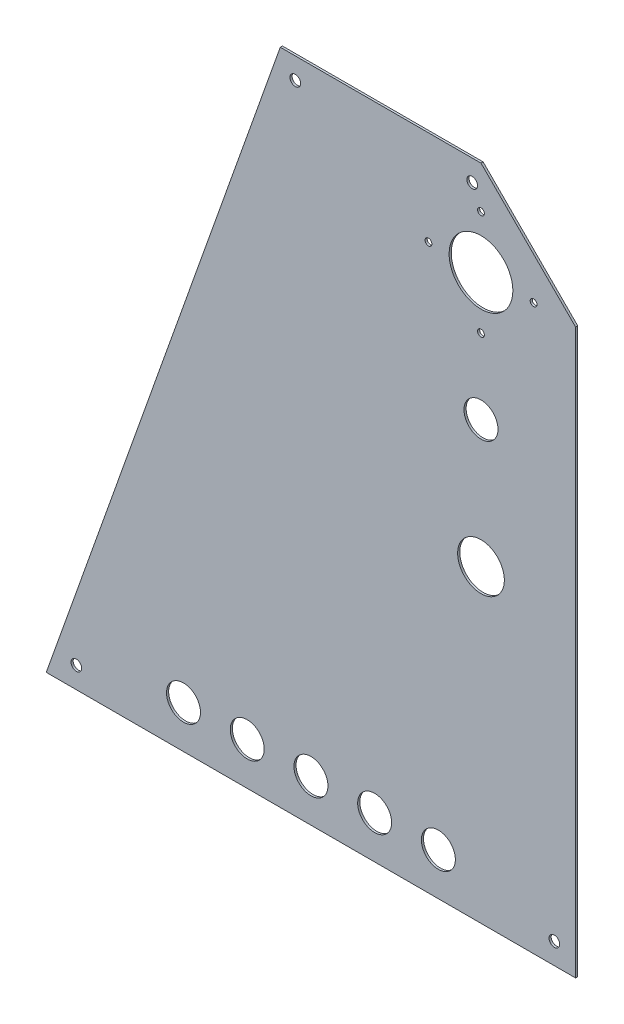
SolidWorks part; units mm, degrees
ref_plane "Front Plane" through (0, 0, 0) normal (1, 0, 0) x (0, 1, 0)
ref_plane "Top Plane" through (0, 0, 0) normal (0, 0, 1) x (0, 1, 0)
ref_plane "Right Plane" through (0, 0, 0) normal (0, 1, 0) x (-1, 0, 0)
sketch "Sketch1" plane through (0, 0, 0) normal (0, 0, 1) x (0, 1, 0)
  line L1 (-155, -125) -> (155, -125)
  line L2 (-155, -125) -> (-155, 125)
  line L3 (-155, 125) -> (155, 125)
  line L4 (155, -125) -> (155, 125)
  line L5 (-155, -125) -> (155, 125) construction
  line L6 (-155, 125) -> (155, -125) construction
  point P0 (0, 0)
  dimension "D1" = 310
  dimension "D2" = 250
extrude "Boss-Extrude1" add sketch "Sketch1" along normal blind 1
sketch "Sketch2" plane through (0, 0, 1) normal (0, 0, 1) x (0, -1, 0)
  line L0 (-155, -14.0477) -> (155, -124.2339)
  line L1 (-155, 125) -> (-155, -125) construction
  line L4 (155, -124.2339) -> (155, 125)
  line L5 (155, 125) -> (-110.4523, 125)
  line L6 (155, 125) -> (-155, 125) construction
  line L7 (-110.4523, 125) -> (-155, 80.4523)
  line L8 (-155, 80.4523) -> (-155, -14.0477)
  line L9 (-155, 80.4523) -> (-155, 125) construction
  line L10 (-155, 125) -> (-110.4523, 125) construction
  dimension "D1" = 63
  dimension "D2" = 329
  dimension "D3" = 94.5
extrude "Cut-Extrude1" cut sketch "Sketch2" against normal through all flip side to cut
sketch "Sketch3" plane through (0, 0, 1) normal (0, 0, 1) x (0, -1, 0)
  line L0 (-155, 80.4523) -> (155, 80.4523) construction
  line L2 (155, -124.2339) -> (155, 125) construction
  line L4 (-110.4523, 125) -> (-155, 80.4523) construction
  line L5 (-155, 80.4523) -> (-110.4523, 80.4523) construction
  line L6 (-110.4523, 80.4523) -> (-110.4523, 125) construction
  line L7 (-110.4523, 55.7035) -> (-85.7035, 80.4523) construction
  line L8 (-85.7035, 80.4523) -> (-110.4523, 105.201) construction
  line L9 (-110.4523, 105.201) -> (-135.201, 80.4523) construction
  line L10 (-135.201, 80.4523) -> (-110.4523, 55.7035) construction
  circle A0 centre (-110.4523, 80.4523) radius 15
  circle A1 centre (-50.4523, 80.4523) radius 8
  circle A2 centre (9.5477, 80.4523) radius 11
  circle A3 centre (-110.4523, 55.7035) radius 1.6
  circle A4 centre (-135.201, 80.4523) radius 1.6
  circle A5 centre (-110.4523, 105.201) radius 1.6
  circle A6 centre (-85.7035, 80.4523) radius 1.6
  point P23 (0, 0)
  dimension "D2" = 30
  dimension "D1" = 16
  dimension "D3" = 22
  dimension "D8" = 3.2
  dimension "D4" = 60
  dimension "D5" = 60
  dimension "D6" = 90
  dimension "D7" = 35
extrude "Cut-Extrude2" cut sketch "Sketch3" against normal through all
sketch "Sketch4" plane through (0, 0, 1) normal (0, 0, 1) x (0, -1, 0)
  line L0 (135, -117.1251) -> (135, 125) construction
  line L1 (-155, -14.0477) -> (155, -124.2339) construction
  line L2 (155, 125) -> (-110.4523, 125) construction
  line L3 (155, -124.2339) -> (155, 125) construction
  circle A0 centre (135, -59.617) radius 8
  circle A1 centre (135, -29.617) radius 8
  circle A2 centre (135, 0.383) radius 8
  circle A3 centre (135, 30.383) radius 8
  circle A4 centre (135, 60.383) radius 8
  point P19 (0, 0)
  point P20 (0, 0)
  point P21 (0, 0)
  point P22 (155, 0.383)
  dimension "D2" = 16
  dimension "D3" = 30
  dimension "D4" = 30
  dimension "D5" = 30
  dimension "D6" = 30
  dimension "D1" = 20
extrude "Cut-Extrude3" cut sketch "Sketch4" against normal through all
sketch "Sketch5" plane through (0, 0, 1) normal (0, 0, 1) x (0, -1, 0)
  line L0 (155, -124.2339) -> (155, 125) construction
  line L3 (155, 125) -> (-110.4523, 125) construction
  line L4 (-155, 80.4523) -> (-155, -14.0477) construction
  line L5 (-155, -14.0477) -> (155, -124.2339) construction
  line L6 (-110.4523, 125) -> (-155, 80.4523) construction
  circle A0 centre (145, -110.0666) radius 2.5
  circle A1 centre (-145, -6.9892) radius 2.5
  circle A2 centre (-145, 76.3101) radius 2.5
  circle A3 centre (145, 115) radius 2.5
  point P12 (143.9698, -114.4475)
  dimension "D1" = 5
  dimension "D2" = 10
  dimension "D3" = 10
  dimension "D4" = 10
  dimension "D5" = 10
  dimension "D6" = 10
  dimension "D7" = 10
  dimension "D8" = 10
  dimension "D9" = 10
extrude "Cut-Extrude4" cut sketch "Sketch5" against normal through all
